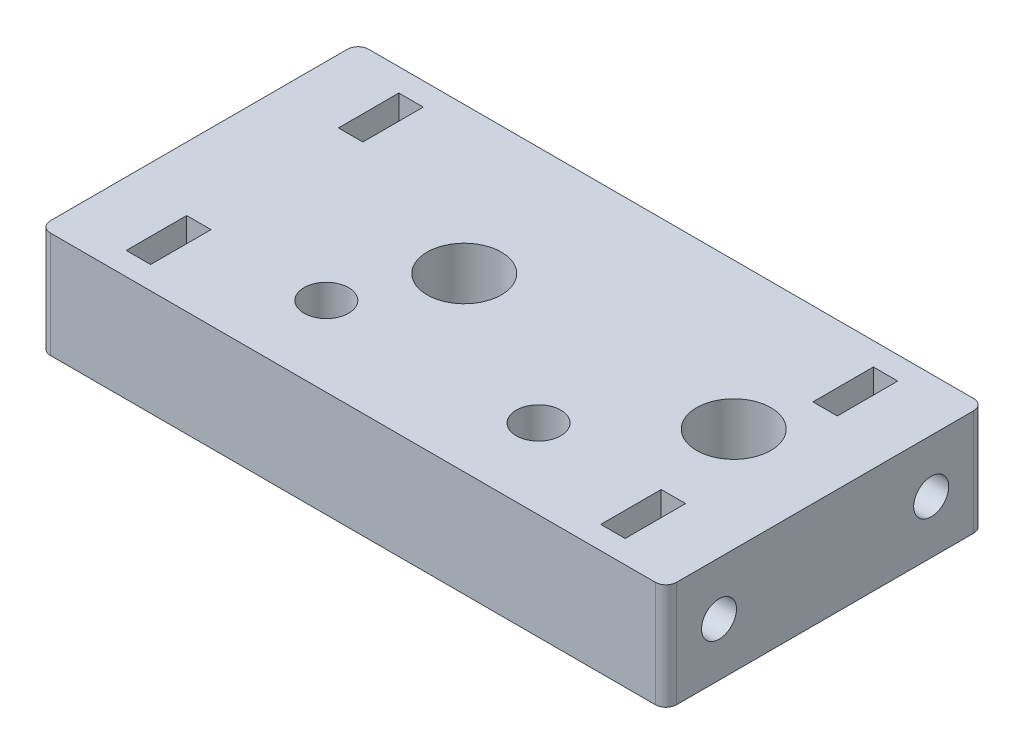
SolidWorks part; units mm, degrees
ref_plane "Front Plane" through (0, 0, 0) normal (0, 0, 1) x (1, 0, 0)
ref_plane "Top Plane" through (0, 0, 0) normal (0, 1, 0) x (1, 0, 0)
ref_plane "Right Plane" through (0, 0, 0) normal (1, 0, 0) x (0, 0, -1)
sketch "Sketch1" plane through (0, 0, 0) normal (0, 1, 0) x (1, 0, 0)
  line L1 (-29.5136, -15) -> (29.5136, -15)
  line L2 (-29.5136, -15) -> (-29.5136, 15)
  line L3 (-29.5136, 15) -> (29.5136, 15)
  line L4 (29.5136, -15) -> (29.5136, 15)
  line L5 (-29.5136, -15) -> (29.5136, 15) construction
  line L6 (-29.5136, 15) -> (29.5136, -15) construction
  point P0 (0, 0)
  dimension "D1" = 59.0272
  dimension "D2" = 30
extrude "Boss-Extrude1" add sketch "Sketch1" along normal blind 10
sketch "Sketch2" plane through (0, 10, 0) normal (0, 1, 0) x (1, 0, 0)
  line L0 (-10, -7.5) -> (10, -7.5) construction
  line L3 (0, 15) -> (0, -15) construction
  line L4 (29.5136, 15) -> (-29.5136, 15) construction
  line L5 (-29.5136, -15) -> (29.5136, -15) construction
  circle A0 centre (-10, -7.5) radius 2.1
  circle A1 centre (10, -7.5) radius 2.1
  point P3 (0, -7.5)
  dimension "D1" = 4.2
  dimension "D2" = 20
  dimension "D3" = 7.5
extrude "Cut-Extrude1" cut sketch "Sketch2" against normal through all
sketch "Sketch3" plane through (29.5136, 0, 0) normal (1, 0, 0) x (0, 0, -1)
  line L0 (0, 10) -> (0, 0) construction
  line L1 (-15, 10) -> (15, 10) construction
  line L2 (-15, 0) -> (15, 0) construction
  line L3 (-10, 5) -> (10, 5) construction
  circle A0 centre (-10, 5) radius 1.65
  circle A1 centre (10, 5) radius 1.65
  point P9 (0, 5)
  dimension "D2" = 3.3
  dimension "D1" = 20
extrude "Cut-Extrude2" cut sketch "Sketch3" against normal blind 12
sketch "Sketch4" plane through (-29.5136, 0, 0) normal (-1, 0, 0) x (0, 0, 1)
  line L0 (0, 10) -> (0, 0) construction
  line L3 (-10, 5) -> (10, 5) construction
  line L4 (-15, 10) -> (15, 10) construction
  circle A0 centre (-10, 5) radius 1.65
  circle A1 centre (10, 5) radius 1.65
  point P9 (0, 5)
  dimension "D2" = 3.3
  dimension "D1" = 20
extrude "Cut-Extrude3" cut sketch "Sketch4" against normal blind 12
ref_plane "Plane1" through (23.5136, 0, 0) normal (1, 0, 0) x (0, 0, -1)
ref_plane "Plane2" through (-23.5136, 0, 0) normal (-1, 0, 0) x (0, 0, 1)
sketch "Sketch5" plane through (23.5136, 0, 0) normal (1, 0, 0) x (0, 0, -1)
  line L0 (-12.85, 6.6454) -> (-12.85, 10)
  line L1 (-7.15, 6.6454) -> (-10, 8.2909) construction
  line L2 (-10, 8.2909) -> (-12.85, 6.6454) construction
  line L3 (-12.85, 6.6454) -> (-12.85, 3.3546)
  line L4 (-12.85, 3.3546) -> (-10, 1.7091)
  line L5 (-10, 1.7091) -> (-7.15, 3.3546)
  line L6 (-7.15, 3.3546) -> (-7.15, 6.6454)
  line L7 (10, 8.2909) -> (7.15, 6.6454) construction
  line L8 (7.15, 6.6454) -> (7.15, 3.3546)
  line L9 (7.15, 3.3546) -> (10, 1.7091)
  line L10 (10, 1.7091) -> (12.85, 3.3546)
  line L11 (12.85, 3.3546) -> (12.85, 6.6454)
  line L12 (12.85, 6.6454) -> (10, 8.2909) construction
  line L13 (-15, 10) -> (15, 10) construction
  line L14 (-12.85, 10) -> (-7.15, 10)
  line L15 (-7.15, 10) -> (-7.15, 6.6454)
  line L16 (7.15, 6.6454) -> (7.15, 10)
  line L17 (7.15, 10) -> (12.85, 10)
  line L18 (12.85, 10) -> (12.85, 6.6454)
  circle A0 centre (-10, 5) radius 2.85 construction
  circle A1 centre (10, 5) radius 2.85 construction
  dimension "D1" = 5.7
extrude "Cut-Extrude4" cut sketch "Sketch5" against normal blind 2.3
sketch "Sketch6" plane through (-23.5136, 0, 0) normal (-1, 0, 0) x (0, 0, 1)
  line L0 (-12.85, 6.6454) -> (-12.85, 10)
  line L1 (-7.15, 6.6454) -> (-10, 8.2909) construction
  line L2 (-10, 8.2909) -> (-12.85, 6.6454) construction
  line L3 (-12.85, 6.6454) -> (-12.85, 3.3546)
  line L4 (-12.85, 3.3546) -> (-10, 1.7091)
  line L5 (-10, 1.7091) -> (-7.15, 3.3546)
  line L6 (-7.15, 3.3546) -> (-7.15, 6.6454)
  line L7 (10, 8.2909) -> (7.15, 6.6454) construction
  line L8 (7.15, 6.6454) -> (7.15, 3.3546)
  line L9 (7.15, 3.3546) -> (10, 1.7091)
  line L10 (10, 1.7091) -> (12.85, 3.3546)
  line L11 (12.85, 3.3546) -> (12.85, 6.6454)
  line L12 (12.85, 6.6454) -> (10, 8.2909) construction
  line L14 (-12.85, 10) -> (-7.15, 10)
  line L15 (-7.15, 10) -> (-7.15, 6.6454)
  line L16 (7.15, 6.6454) -> (7.15, 10)
  line L17 (7.15, 10) -> (12.85, 10)
  line L18 (12.85, 10) -> (12.85, 6.6454)
  line L19 (-15, 10) -> (15, 10) construction
  circle A0 centre (-10, 5) radius 2.85 construction
  circle A1 centre (10, 5) radius 2.85 construction
  circle A2 centre (-10, 5) radius 1.65 construction
  circle A3 centre (-10, 5) radius 1.65 construction
  circle A5 centre (10, 5) radius 1.65 construction
  circle A6 centre (10, 5) radius 1.65 construction
  dimension "D1" = 5.7
extrude "Cut-Extrude5" cut sketch "Sketch6" against normal blind 2.3
sketch "Sketch7" plane through (0, 10, 0) normal (0, 1, 0) x (1, 0, 0)
  line L0 (29.5136, -15) -> (29.5136, 15) construction
  line L1 (-29.5136, -15) -> (29.5136, -15) construction
  line L2 (19.7, 1.2) -> (-5.7, 1.2) construction
  circle A0 centre (19.7, 1.2) radius 3.5
  circle A1 centre (-5.7, 1.2) radius 3.5
  dimension "D3" = 7
  dimension "D1" = 9.8136
  dimension "D2" = 16.2
  dimension "D4" = 25.4
extrude "Cut-Extrude6" cut sketch "Sketch7" against normal through all
fillet "Fillet1" radius 1 4 edges at (-29.5136, 5, 15) (-29.5136, 5, -15) (29.5136, 5, -15) (29.5136, 5, 15)
